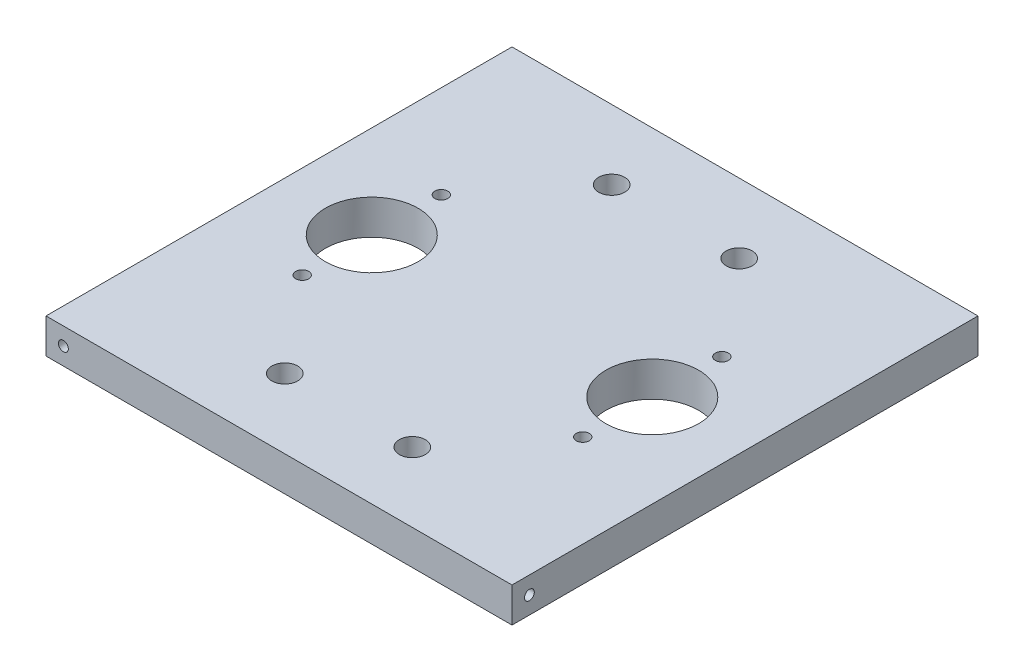
SolidWorks part; units mm, degrees
material "6061-T6 (SS)"
ref_plane "Front" through (0, 0, 0) normal (0, 0, 1) x (1, 0, 0)
ref_plane "Top" through (0, 0, 0) normal (0, 1, 0) x (1, 0, 0)
ref_plane "Right" through (0, 0, 0) normal (1, 0, 0) x (0, 0, -1)
sketch "Sketch1" plane through (0, 0, 0) normal (0, 1, 0) x (1, 0, 0)
  line L1 (0, 0) -> (127.635, 0)
  line L2 (0, 0) -> (0, 127.635)
  line L3 (0, 127.635) -> (127.635, 127.635)
  line L4 (127.635, 0) -> (127.635, 127.635)
  dimension "D1" = 127.635
  dimension "D2" = 127.635
extrude "Main Plate" add sketch "Sketch1" along normal blind 9.525
sketch "Sketch2" plane through (0, 9.525, 0) normal (0, 1, 0) x (1, 0, 0)
  line L0 (0, 127.635) -> (0, 0) construction
  line L1 (127.635, 127.635) -> (0, 127.635) construction
  circle A0 centre (46.355, 108.585) radius 3.556
  dimension "D1" = 7.112
  dimension "D2" = 46.355
  dimension "D3" = 19.05
extrude "U-Bolt Hole" cut sketch "Sketch2" against normal blind 12.7
pattern_linear "U-Bolt Pattern" count 2 spacing 34.925 along (1, 0, 0) count 2 spacing 89.535 along (0, 0, 1) of "U-Bolt Hole"
sketch "Sketch3" plane through (0, 9.525, 0) normal (0, 1, 0) x (1, 0, 0)
  line L0 (0, 127.635) -> (0, 0) construction
  line L1 (0, 0) -> (127.635, 0) construction
  circle A0 centre (25.4, 44.7675) radius 1.778
  dimension "D1" = 3.556
  dimension "D2" = 25.4
  dimension "D3" = 44.7675
extrude "Raptor Bolt Hole" cut sketch "Sketch3" against normal blind 12.7
pattern_linear "Raptor Bolt Pattern" count 2 spacing 38.1 along (0, 0, -1) count 2 spacing 76.835 along (1, 0, 0) of "Raptor Bolt Hole"
sketch "Sketch4" plane through (0, 9.525, 0) normal (0, 1, 0) x (1, 0, 0)
  line L0 (0, 127.635) -> (0, 0) construction
  line L1 (127.635, 127.635) -> (0, 127.635) construction
  circle A0 centre (25.4, 63.8175) radius 12.7
  dimension "D1" = 25.4
  dimension "D2" = 63.8175
  dimension "D3" = 25.4
extrude "Co2 Cylinder Hole" cut sketch "Sketch4" against normal blind 12.7
pattern_linear "Co2 Pattern" count 2 spacing 76.835 along (1, 0, 0) of "Co2 Cylinder Hole"
sketch "Sketch5" plane through (0, 0, 0) normal (0, 0, 1) x (1, 0, 0)
  line L0 (0, 9.525) -> (0, 0) construction
  line L1 (0, 0) -> (127.635, 0) construction
  circle A0 centre (4.7625, 4.7625) radius 1.3526
  dimension "D1" = 2.7051
  dimension "D2" = 4.7625
  dimension "D3" = 4.7625
extrude "Frame attachment hole 1" cut sketch "Sketch5" against normal blind 12.7
sketch "Sketch6" plane through (0, 0, 0) normal (-1, 0, 0) x (0, 0, 1)
  line L2 (-127.635, 0) -> (0, 0) construction
  line L3 (-127.635, 9.525) -> (-127.635, 0) construction
  circle A0 centre (-122.8725, 4.7625) radius 1.3525
  dimension "D1" = 2.7051
  dimension "D2" = 4.7625
  dimension "D3" = 4.7625
extrude "Frame attachment hole 2" cut sketch "Sketch6" against normal blind 12.7
sketch "Sketch7" plane through (0, 0, -127.635) normal (0, 0, -1) x (-1, 0, 0)
  line L2 (-127.635, 0) -> (0, 0) construction
  line L3 (-127.635, 9.525) -> (-127.635, 0) construction
  circle A0 centre (-122.8725, 4.7625) radius 1.3526
  dimension "D1" = 2.7051
  dimension "D2" = 4.7625
  dimension "D3" = 4.7625
extrude "Frame attachment hole 3" cut sketch "Sketch7" against normal blind 12.7
sketch "Sketch8" plane through (127.635, 0, 0) normal (1, 0, 0) x (0, 0, -1)
  line L2 (0, 0) -> (127.635, 0) construction
  line L3 (0, 9.525) -> (0, 0) construction
  circle A0 centre (4.7625, 4.7625) radius 1.3526
  dimension "D1" = 2.7051
  dimension "D2" = 4.7625
  dimension "D3" = 4.7625
extrude "Frame attachment hole 4" cut sketch "Sketch8" against normal blind 12.7
